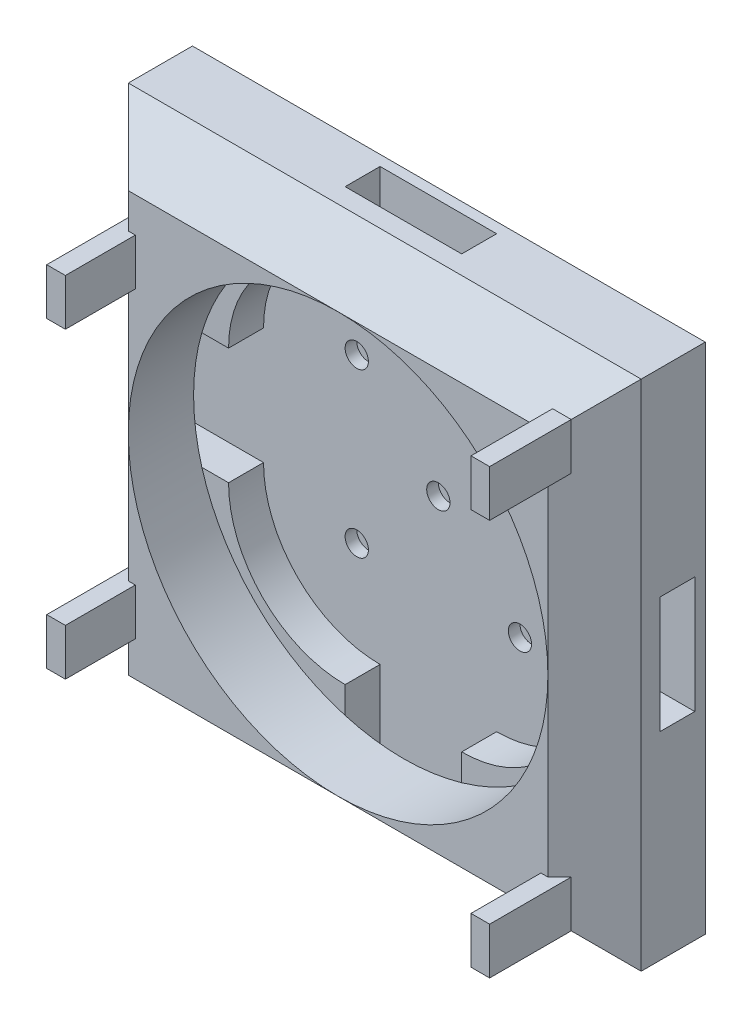
SolidWorks part; units mm, degrees
material "3.0205 (EN-AW 1200)"
ref_plane "정면" through (0, 0, 0) normal (0, 0, 1) x (1, 0, 0)
ref_plane "윗면" through (0, 0, 0) normal (0, 1, 0) x (1, 0, 0)
ref_plane "우측면" through (0, 0, 0) normal (1, 0, 0) x (0, 0, -1)
sketch "스케치1" plane through (0, 0, 0) normal (0, 0, 1) x (1, 0, 0)
  line L1 (-110, 110) -> (110, 110)
  line L2 (-110, 110) -> (-110, -110)
  line L3 (-110, -110) -> (110, -110)
  line L4 (110, 110) -> (110, -110)
  line L5 (-110, 110) -> (110, -110) construction
  line L6 (-110, -110) -> (110, 110) construction
  point P0 (0, 0)
  dimension "D1" = 220
  dimension "D2" = 220
extrude "보스-돌출1" add sketch "스케치1" along normal blind 20 draft 45
sketch "스케치2" plane through (0, 0, 20) normal (0, 0, 1) x (1, 0, 0)
  line L0 (90, 90) -> (-90, 90) construction
  line L1 (-95, 75) -> (-87, 75)
  line L2 (-95, 75) -> (-95, 55)
  line L3 (-95, 55) -> (-87, 55)
  line L4 (-87, 75) -> (-87, 55)
  line L5 (-90, -90) -> (90, -90) construction
  line L6 (-90, 90) -> (-90, -90) construction
  line L11 (92.1899, 0) -> (-92.1899, 0) construction
  line L16 (-87, -75) -> (-87, -55)
  line L17 (-95, -55) -> (-87, -55)
  line L18 (-95, -75) -> (-95, -55)
  line L19 (-95, -75) -> (-87, -75)
  line L21 (87, 95) -> (95, 95)
  line L22 (87, 95) -> (87, 75)
  line L23 (87, 75) -> (95, 75)
  line L24 (95, 95) -> (95, 75)
  line L25 (87, -75) -> (95, -75)
  line L26 (87, -75) -> (87, -95)
  line L27 (87, -95) -> (95, -95)
  line L28 (95, -75) -> (95, -95)
  line L32 (90, -90) -> (90, 90) construction
  dimension "D1" = 8
  dimension "D2" = 20
  dimension "D3" = 15
  dimension "D4" = 3
  dimension "D5" = 5
  dimension "D6" = 20
  dimension "D7" = 20
  dimension "D8" = 5
  dimension "D9" = 8
  dimension "D10" = 8
  dimension "D11" = 3
  dimension "D12" = 3
extrude "보스-돌출2" add sketch "스케치2" along normal blind 30 and the other way up to surface (20 mm away) other way up to face at (0, 0, 0)
sketch "스케치3" plane through (0, 0, 20) normal (0, 0, 1) x (1, 0, 0)
  text T0 "WAYUP\r\n" font "Century Gothic" height 20
sketch "스케치4" plane through (0, 0, 0) normal (0, 0, -1) x (-1, 0, 0)
  line L1 (-110, 110) -> (110, 110)
  line L2 (-110, 110) -> (-110, -110)
  line L3 (-110, -110) -> (110, -110)
  line L4 (110, 110) -> (110, -110)
extrude "보스-돌출3" add sketch "스케치4" along normal blind 30
ref_plane "평면1" through (0, 0, -23) normal (0, 0, -1) x (-1, 0, 0)
sketch "스케치6" plane through (0, 0, -23) normal (0, 0, -1) x (-1, 0, 0)
  line L0 (-110, 25) -> (-75, 25)
  line L1 (-110, 110) -> (-110, -110) construction
  line L2 (25, 110) -> (25, 75)
  line L3 (110, -25) -> (75, -25)
  line L4 (-25, -110) -> (-25, -75)
  line L5 (-75, -25) -> (-110, -25)
  line L6 (-110, -25) -> (-110, 25)
  line L7 (25, -75) -> (25, -110)
  line L8 (-110, -110) -> (110, -110) construction
  line L9 (25, -110) -> (-25, -110)
  line L10 (110, -25) -> (110, 25)
  line L11 (110, -110) -> (110, 110) construction
  line L12 (110, 25) -> (75, 25)
  line L13 (25, 110) -> (-25, 110)
  line L14 (110, 110) -> (-110, 110) construction
  line L15 (-25, 110) -> (-25, 75)
  arc A0 (-75, 25) -> (-25, 75) centre (-25, 25) cw
  arc A1 (25, 75) -> (75, 25) centre (25, 25) cw
  arc A2 (75, -25) -> (25, -75) centre (25, -25) cw
  arc A3 (-25, -75) -> (-75, -25) centre (-25, -25) cw
  point P21 (0, 0)
  dimension "D3" = 50
  dimension "D2" = 50
  dimension "D4" = 0
  dimension "D1" = 4
extrude "컷-돌출1" cut sketch "스케치6" against normal blind 15
sketch "스케치7" plane through (0, 0, 20) normal (0, 0, 1) x (1, 0, 0)
  circle A0 centre (0, 0) radius 90
  dimension "D1" = 180
extrude "컷-돌출2" cut sketch "스케치7" against normal blind 28
sketch "스케치9" plane through (0, 0, -23) normal (0, 0, 1) x (1, 0, 0)
  line L4 (11, 0) -> (-11, 0) construction
  circle A0 centre (-35, 35) radius 5
  circle A1 centre (0, 0) radius 5
  circle A2 centre (35, 35) radius 5
  circle A5 centre (-35, -35) radius 5 [skipped]
  circle A6 centre (35, -35) radius 5 [skipped]
  circle A7 centre (35, -35) radius 5
  circle A8 centre (-35, -35) radius 5
  point P15 (0, 0)
  dimension "D1" = 10
  dimension "D7" = 10
  dimension "D2" = 40
  dimension "D3" = 40
  dimension "D5" = 40
  dimension "D6" = 40
  dimension "D4" = 4
extrude "컷-돌출3" cut sketch "스케치9" against normal blind 5
sketch "스케치10" plane through (0, 110, 0) normal (0, 1, 0) x (1, 0, 0)
  line L0 (-110, 30) -> (-110, 27.5)
  line L1 (-110, 30) -> (-110, 0) construction
  line L2 (-110, 27.5) -> (-107.5, 30)
  line L3 (-110, 30) -> (110, 30) construction
  line L4 (-107.5, 30) -> (-110, 30)
  dimension "D1" = 2.5
  dimension "D2" = 2.5
extrude "컷-돌출4" cut sketch "스케치10" against normal through all
sketch "스케치11" plane through (0, 0, 0) normal (0, 1, 0) x (1, 0, 0)
  line L0 (0, -68.4326) -> (0, 99.1854) construction
pattern_circular "원형 패턴2" count 4 over 360 about axis through (0, 0, 68.4326) along (0, 0, -1) of "컷-돌출4" reverse direction yes
